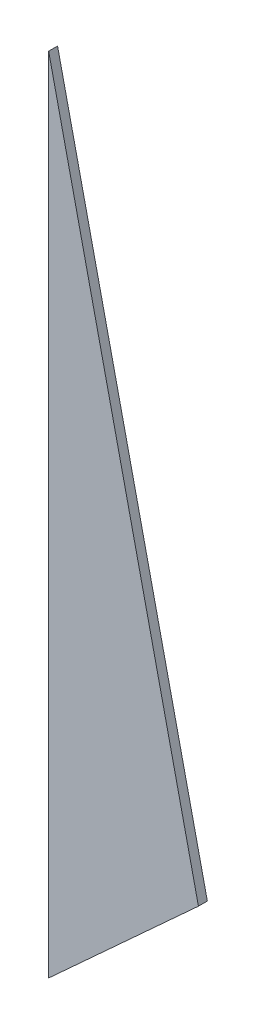
SolidWorks part; units mm, degrees
ref_plane "Front Plane" through (0, 0, 0) normal (0, 0, 1) x (1, 0, 0)
ref_plane "Top Plane" through (0, 0, 0) normal (0, 1, 0) x (1, 0, 0)
ref_plane "Right Plane" through (0, 0, 0) normal (1, 0, 0) x (0, 0, -1)
sketch "Sketch1" plane through (0, 0, 0) normal (0, 0, 1) x (1, 0, 0)
  line L0 (0, -45) -> (0, 45)
  line L1 (0, 45) -> (16.7943, -29.6323)
  line L2 (0, -45) -> (16.7943, -29.6323)
  line L4 (18, 250.753) -> (18, -45) construction
  point P4 (0, 0)
extrude "Boss-Extrude1" add sketch "Sketch1" along normal mid plane 1
